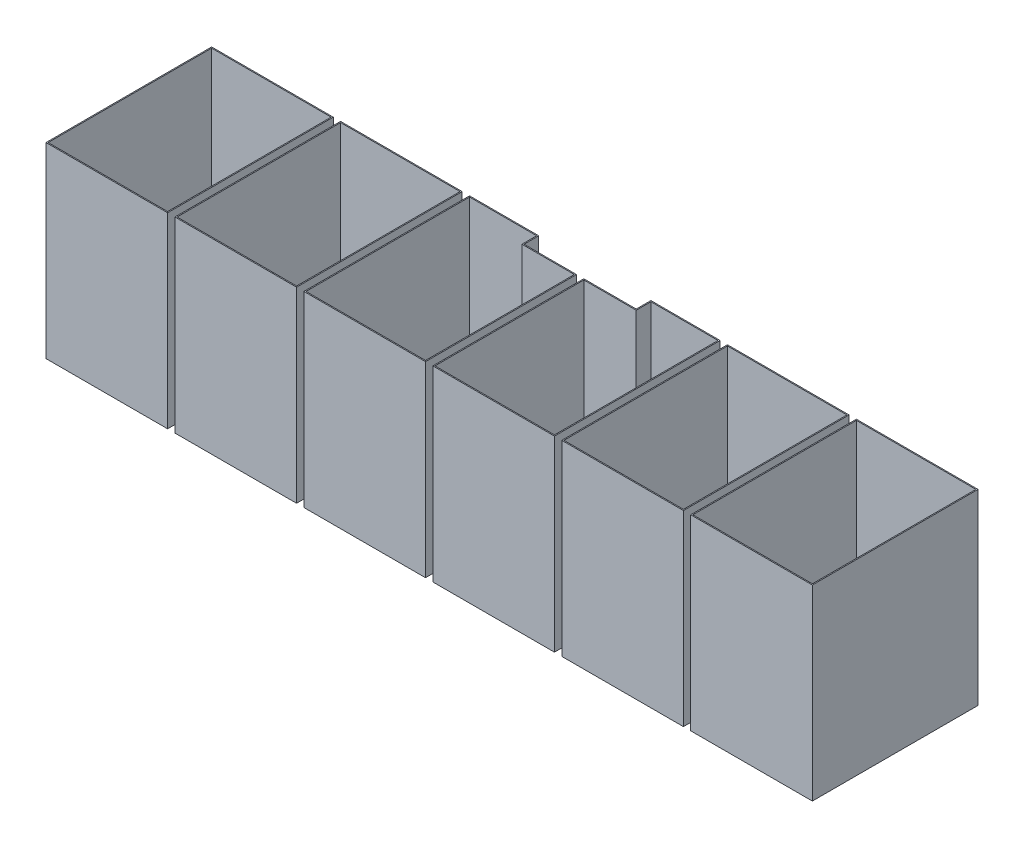
SolidWorks part; units mm, degrees
ref_plane "Front Plane" through (0, 0, 0) normal (0, 0, 1) x (1, 0, 0)
ref_plane "Top Plane" through (0, 0, 0) normal (0, 1, 0) x (1, 0, 0)
ref_plane "Right Plane" through (0, 0, 0) normal (1, 0, 0) x (0, 0, -1)
sketch "Sketch2" plane through (0, 0, 0) normal (0, 1, 0) x (1, 0, 0)
  line L4 (1612.9, 50.8) -> (3086.1, 50.8)
  line L5 (3086.1, 50.8) -> (3086.1, 2057.4)
  line L6 (3086.1, 2057.4) -> (1612.9, 2057.4)
  line L7 (1612.9, 2057.4) -> (1612.9, 50.8)
  line L8 (1612.9, 50.8) -> (3086.1, 50.8)
  line L9 (3086.1, 50.8) -> (3086.1, 2057.4)
  line L10 (3086.1, 2057.4) -> (1612.9, 2057.4)
  line L11 (1612.9, 2057.4) -> (1612.9, 50.8)
  line L12 (1524, 2057.4) -> (50.8, 2057.4)
  line L13 (50.8, 2057.4) -> (50.8, 50.8)
  line L14 (4013.2, 1879.6) -> (4013.2, 2057.4)
  line L15 (4648.2, 1879.6) -> (4013.2, 1879.6)
  line L16 (4648.2, 50.8) -> (4648.2, 1879.6)
  line L17 (3175, 50.8) -> (4648.2, 50.8)
  line L18 (3175, 2057.4) -> (3175, 50.8)
  line L19 (4013.2, 2057.4) -> (3175, 2057.4)
  line L20 (4013.2, 1879.6) -> (4013.2, 2057.4)
  line L21 (4648.2, 1879.6) -> (4013.2, 1879.6)
  line L22 (4648.2, 50.8) -> (4648.2, 1879.6)
  line L23 (3175, 50.8) -> (4648.2, 50.8)
  line L24 (3175, 2057.4) -> (3175, 50.8)
  line L25 (4013.2, 2057.4) -> (3175, 2057.4)
  line L26 (50.8, 50.8) -> (1524, 50.8)
  line L27 (1524, 50.8) -> (1524, 2057.4)
  line L28 (1524, 2057.4) -> (50.8, 2057.4)
  line L29 (50.8, 2057.4) -> (50.8, 50.8)
  line L30 (50.8, 50.8) -> (1524, 50.8)
  line L31 (1524, 50.8) -> (1524, 2057.4)
  line L32 (6299.2, 2057.4) -> (6299.2, 50.8)
  line L33 (7772.4, 2057.4) -> (6299.2, 2057.4)
  line L34 (7772.4, 50.8) -> (7772.4, 2057.4)
  line L35 (6299.2, 50.8) -> (7772.4, 50.8)
  line L36 (6299.2, 2057.4) -> (6299.2, 50.8)
  line L37 (7772.4, 2057.4) -> (6299.2, 2057.4)
  line L38 (7772.4, 50.8) -> (7772.4, 2057.4)
  line L39 (6299.2, 50.8) -> (7772.4, 50.8)
  line L40 (3073.4, 2044.7) -> (1625.6, 2044.7)
  line L41 (3073.4, 63.5) -> (3073.4, 2044.7)
  line L42 (5372.1, 2057.4) -> (5372.1, 1879.6)
  line L43 (6210.3, 2057.4) -> (5372.1, 2057.4)
  line L44 (6210.3, 50.8) -> (6210.3, 2057.4)
  line L45 (4737.1, 50.8) -> (6210.3, 50.8)
  line L46 (4737.1, 1879.6) -> (4737.1, 50.8)
  line L47 (5372.1, 1879.6) -> (4737.1, 1879.6)
  line L48 (5372.1, 2057.4) -> (5372.1, 1879.6)
  line L49 (6210.3, 2057.4) -> (5372.1, 2057.4)
  line L50 (6210.3, 50.8) -> (6210.3, 2057.4)
  line L51 (4737.1, 50.8) -> (6210.3, 50.8)
  line L52 (4737.1, 1879.6) -> (4737.1, 50.8)
  line L53 (5372.1, 1879.6) -> (4737.1, 1879.6)
  line L54 (1625.6, 63.5) -> (3073.4, 63.5)
  line L55 (1625.6, 2044.7) -> (1625.6, 63.5)
  line L56 (3073.4, 2044.7) -> (1625.6, 2044.7)
  line L57 (3073.4, 63.5) -> (3073.4, 2044.7)
  line L58 (1625.6, 63.5) -> (3073.4, 63.5)
  line L59 (1625.6, 2044.7) -> (1625.6, 63.5)
  line L60 (9334.5, 50.8) -> (9334.5, 2057.4)
  line L61 (7861.3, 50.8) -> (9334.5, 50.8)
  line L62 (7861.3, 2057.4) -> (7861.3, 50.8)
  line L63 (9334.5, 2057.4) -> (7861.3, 2057.4)
  line L64 (9334.5, 50.8) -> (9334.5, 2057.4)
  line L65 (7861.3, 50.8) -> (9334.5, 50.8)
  line L66 (7861.3, 2057.4) -> (7861.3, 50.8)
  line L67 (9334.5, 2057.4) -> (7861.3, 2057.4)
  line L68 (1511.3, 2044.7) -> (63.5, 2044.7)
  line L69 (1511.3, 63.5) -> (1511.3, 2044.7)
  line L70 (63.5, 63.5) -> (1511.3, 63.5)
  line L71 (63.5, 2044.7) -> (63.5, 63.5)
  line L72 (1511.3, 2044.7) -> (63.5, 2044.7)
  line L73 (1511.3, 63.5) -> (1511.3, 2044.7)
  line L74 (63.5, 63.5) -> (1511.3, 63.5)
  line L75 (63.5, 2044.7) -> (63.5, 63.5)
  line L76 (9321.8, 2044.7) -> (7874, 2044.7)
  line L77 (9321.8, 63.5) -> (9321.8, 2044.7)
  line L78 (7874, 63.5) -> (9321.8, 63.5)
  line L79 (7874, 2044.7) -> (7874, 63.5)
  line L80 (9321.8, 2044.7) -> (7874, 2044.7)
  line L81 (9321.8, 63.5) -> (9321.8, 2044.7)
  line L82 (7874, 63.5) -> (9321.8, 63.5)
  line L83 (7874, 2044.7) -> (7874, 63.5)
  line L84 (7759.7, 2044.7) -> (6311.9, 2044.7)
  line L85 (7759.7, 63.5) -> (7759.7, 2044.7)
  line L86 (6311.9, 63.5) -> (7759.7, 63.5)
  line L87 (6311.9, 2044.7) -> (6311.9, 63.5)
  line L88 (7759.7, 2044.7) -> (6311.9, 2044.7)
  line L89 (7759.7, 63.5) -> (7759.7, 2044.7)
  line L90 (6311.9, 63.5) -> (7759.7, 63.5)
  line L91 (6311.9, 2044.7) -> (6311.9, 63.5)
  line L94 (5384.8, 1866.9) -> (4749.8, 1866.9)
  line L95 (5384.8, 2044.7) -> (5384.8, 1866.9)
  line L96 (6197.6, 2044.7) -> (5384.8, 2044.7)
  line L97 (6197.6, 63.5) -> (6197.6, 2044.7)
  line L98 (4749.8, 63.5) -> (6197.6, 63.5)
  line L99 (4749.8, 1866.9) -> (4749.8, 63.5)
  line L100 (5384.8, 1866.9) -> (4749.8, 1866.9)
  line L101 (5384.8, 2044.7) -> (5384.8, 1866.9)
  line L102 (6197.6, 2044.7) -> (5384.8, 2044.7)
  line L103 (6197.6, 63.5) -> (6197.6, 2044.7)
  line L104 (4749.8, 63.5) -> (6197.6, 63.5)
  line L105 (4749.8, 1866.9) -> (4749.8, 63.5)
  line L106 (3187.7, 63.5) -> (4635.5, 63.5)
  line L107 (3187.7, 2044.7) -> (3187.7, 63.5)
  line L108 (4000.5, 2044.7) -> (3187.7, 2044.7)
  line L109 (4000.5, 1866.9) -> (4000.5, 2044.7)
  line L110 (4635.5, 1866.9) -> (4000.5, 1866.9)
  line L111 (4635.5, 63.5) -> (4635.5, 1866.9)
  line L112 (3187.7, 63.5) -> (4635.5, 63.5)
  line L113 (3187.7, 2044.7) -> (3187.7, 63.5)
  line L114 (4000.5, 2044.7) -> (3187.7, 2044.7)
  line L115 (4000.5, 1866.9) -> (4000.5, 2044.7)
  line L116 (4635.5, 1866.9) -> (4000.5, 1866.9)
  line L117 (4635.5, 63.5) -> (4635.5, 1866.9)
  dimension "D1" = 0
  dimension "D2" = 0
  dimension "D3" = 0
  dimension "D4" = 0
  dimension "D5" = 0
  dimension "D6" = 0
  dimension "D7" = 0
  dimension "D8" = 0
  dimension "D9" = 0
  dimension "D10" = 0
  dimension "D11" = 0
  dimension "D12" = 0
extrude "Boss-Extrude1" add sketch "Sketch2" along normal up to surface (2266.95 mm away)
